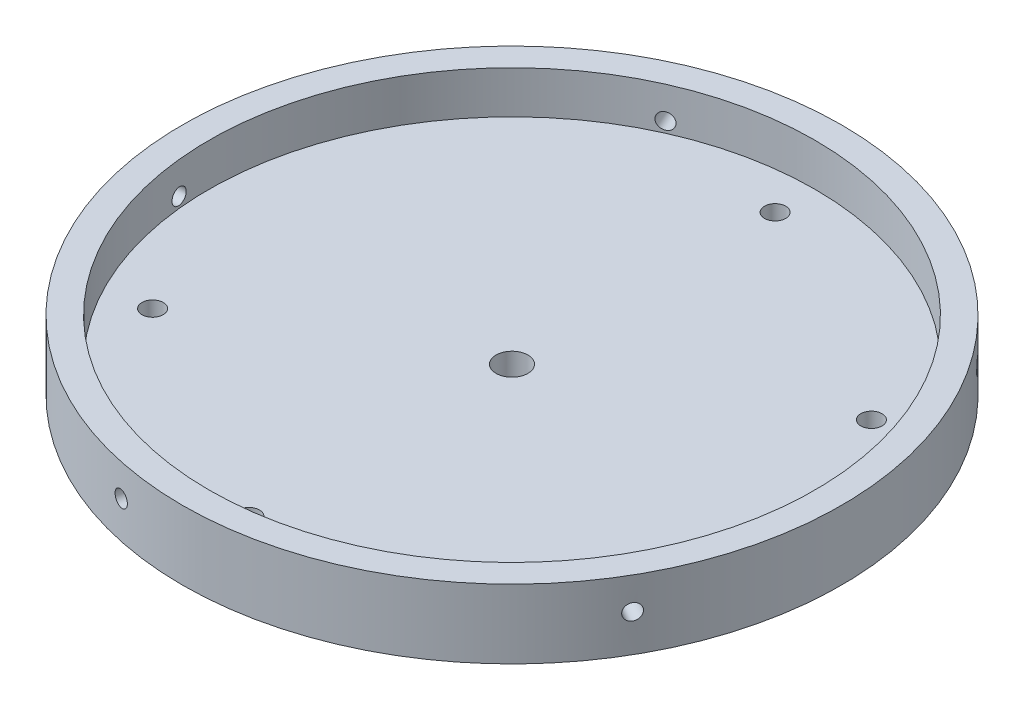
SolidWorks part; units mm, degrees
material "Polyetheretherketone (PEEK)"
ref_plane "Front Plane" through (0, 0, 0) normal (0, 0, 1) x (1, 0, 0)
ref_plane "Top Plane" through (0, 0, 0) normal (0, 1, 0) x (1, 0, 0)
ref_plane "Right Plane" through (0, 0, 0) normal (1, 0, 0) x (0, 0, -1)
sketch "Sketch1" plane through (0, 0, 0) normal (0, 1, 0) x (1, 0, 0)
  circle A0 centre (0, 0) radius 62
  dimension "D1" = 124
extrude "Boss-Extrude1" add sketch "Sketch1" along normal blind 5
sketch "Sketch2" plane through (0, 5, 0) normal (0, 1, 0) x (1, 0, 0)
  circle A0 centre (0, 49.5) radius 2
  dimension "D2" = 4
  dimension "D1" = 49.5
extrude "Cut-Extrude1" cut sketch "Sketch2" against normal blind 5 contours A0
pattern_circular "CirPattern1" count 2 every 120 about axis through (0, 5, 0) along (0, 1, 0) of "Cut-Extrude1"
sketch "Sketch4" plane through (0, 5, 0) normal (0, 1, 0) x (1, 0, 0)
  line L0 (0, 49.5) -> (-42.8683, -24.75) construction
  line L1 (0, 0) -> (-23.6703, -40.9981) construction
ref_plane "Plane1" through (0, 0, 0) normal (-0.866, 0, -0.5) x (-0.5, 0, 0.866)
mirror "Mirror1" about plane through (0, 0, 0) normal (-0.866, 0, -0.5) of "Cut-Extrude1", "CirPattern1"
sketch "Sketch5" plane through (0, 5, 0) normal (0, 1, 0) x (1, 0, 0)
  circle A0 centre (0, 0) radius 62
  circle A1 centre (0, 0) radius 57
  dimension "D1" = 5
extrude "Boss-Extrude2" add sketch "Sketch5" along normal blind 8
sketch "Sketch6" plane through (0, 0, 0) normal (-0.866, 0, -0.5) x (-0.5, 0, 0.866)
  line L0 (57, 13) -> (-57, 13) construction
  circle A0 centre (0, 7) radius 1.5
  dimension "D1" = 3
  dimension "D2" = 6
extrude "Cut-Extrude2" cut sketch "Sketch6" against normal blind 90 and the other way blind 1 contours A0
pattern_circular "CirPattern2" count 5 every 72 about axis through (0, 13, 0) along (0, 1, 0) of "Cut-Extrude2"
sketch "Sketch7" plane through (0, 5, 0) normal (0, 1, 0) x (1, 0, 0)
  circle A0 centre (0, 0) radius 3
  dimension "D1" = 6
extrude "Cut-Extrude3" cut sketch "Sketch7" against normal blind 10
sketch "Sketch9" plane through (0, 0, 0) normal (0, 1, 0) x (1, 0, 0)
  line L0 (0, 0) -> (53.6936, -31)
  line L2 (53.6936, -31) -> (85.1545, 23.4919) construction
